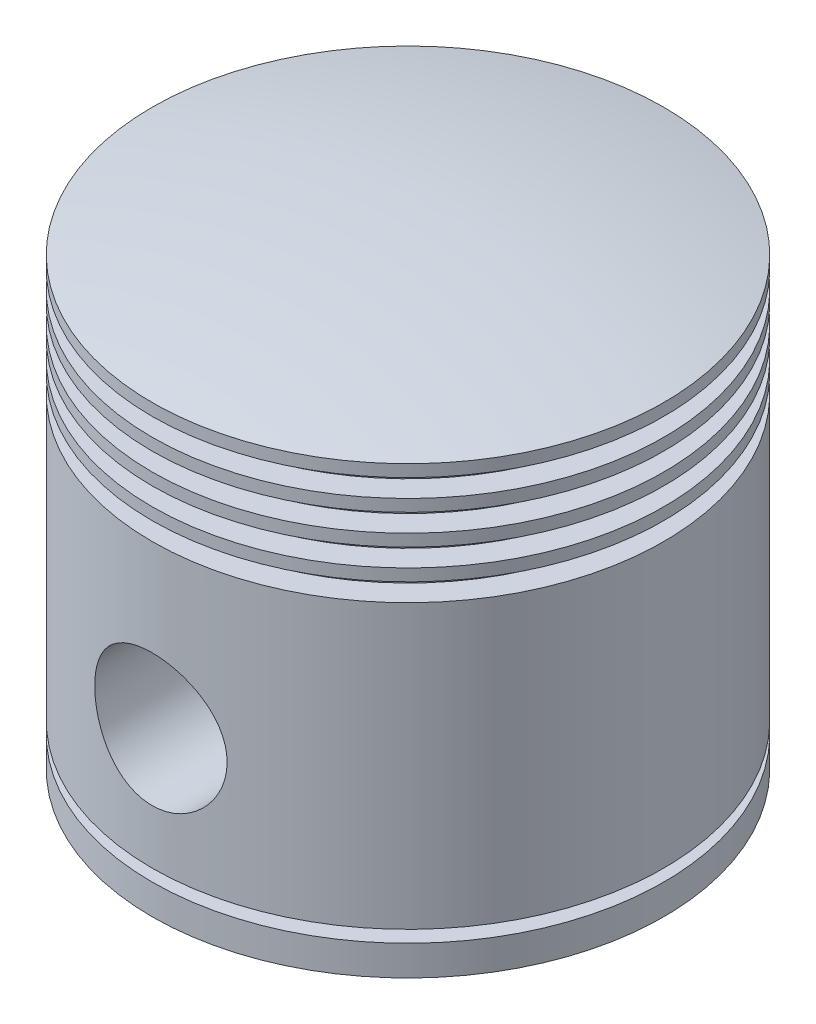
SolidWorks part; units mm, degrees
ref_plane "Front Plane" through (0, 0, 0) normal (0, 0, 1) x (1, 0, 0)
ref_plane "Top Plane" through (0, 0, 0) normal (0, 1, 0) x (1, 0, 0)
ref_plane "Right Plane" through (0, 0, 0) normal (1, 0, 0) x (0, 0, -1)
sketch "Sketch1" plane through (0, 0, 0) normal (0, 0, 1) x (1, 0, 0)
  line L0 (42.5, 7) -> (42.5, 5)
  line L1 (42.5, 5) -> (38.5, 5)
  line L2 (38.5, 5) -> (38.5, 2)
  line L3 (38.5, 2) -> (42.5, 2)
  line L4 (42.5, 2) -> (42.5, 0)
  line L5 (42.5, 0) -> (38.5, 0)
  line L6 (38.5, 0) -> (38.5, -3)
  line L7 (38.5, -3) -> (42.5, -3)
  line L8 (42.5, -3) -> (42.5, -5)
  line L9 (42.5, -5) -> (38.5, -5)
  line L10 (38.5, -5) -> (38.5, -8)
  line L11 (38.5, -8) -> (42.5, -8)
  line L12 (42.5, -8) -> (42.5, -10)
  line L13 (42.5, -10) -> (38.5, -10)
  line L14 (38.5, -10) -> (38.5, -13)
  line L15 (38.5, -13) -> (42.5, -13)
  line L16 (42.5, -13) -> (42.5, -60)
  line L17 (42.5, -60) -> (38.5, -60)
  line L18 (38.5, -60) -> (38.5, -62)
  line L19 (38.5, -62) -> (42.5, -62)
  line L20 (42.5, -62) -> (42.5, -67)
  line L21 (42.5, -67) -> (37, -67)
  line L22 (37, -67) -> (37, 0)
  line L23 (37, 0) -> (0, 0)
  line L24 (0, 0) -> (0, 11.8404)
  line L25 (0, 0) -> (0, 45.5265) construction
  arc A0 (0, 11.8404) -> (42.5, 7) centre (0, -177.1596) cw
  arc A1 (0, 11.8404) -> (-42.5, 7) centre (0, -177.1596) ccw
  point P31 (0, 0)
  point P32 (0, 0)
  point P33 (0, 14.2393)
  dimension "D5" = 189
  dimension "D1" = 3
  dimension "D2" = 2
  dimension "D3" = 4
  dimension "D4" = 42.5
  dimension "D6" = 37
  dimension "D7" = 7
  dimension "D8" = 67
  dimension "D9" = 2
revolve "Revolve1" add sketch "Sketch1" angle 360 about L25
sketch "Sketch2" plane through (0, 0, 0) normal (0, 0, 1) x (1, 0, 0)
  line L0 (-42.5, -67) -> (42.5, -67) construction
  circle A0 centre (0, -40) radius 18
  point P4 (0, 0)
  dimension "D1" = 36
  dimension "D2" = 27
extrude "Boss-Extrude1" add sketch "Sketch2" along normal up to surface (7.3265 mm away) from offset 25 up to face at (0, 0, -37)
extrude "Boss-Extrude2" add sketch "Sketch2<2>" against normal up to surface (7.3265 mm away) from offset 25 up to face at (0, 0, -37) offset against normal yes
sketch "Sketch2<2>" plane through (0, 0, 0) normal (0, 0, 1) x (1, 0, 0) same geometry as "Sketch2"
sketch "Sketch3" plane through (0, 0, 0) normal (0, 0, 1) x (1, 0, 0)
  line L0 (-42.5, -67) -> (42.5, -67) construction
  circle A0 centre (0, -40) radius 11
  point P4 (0, 0)
  dimension "D1" = 22
  dimension "D2" = 27
extrude "Cut-Extrude1" cut sketch "Sketch3" against normal through all both and the other way through all
